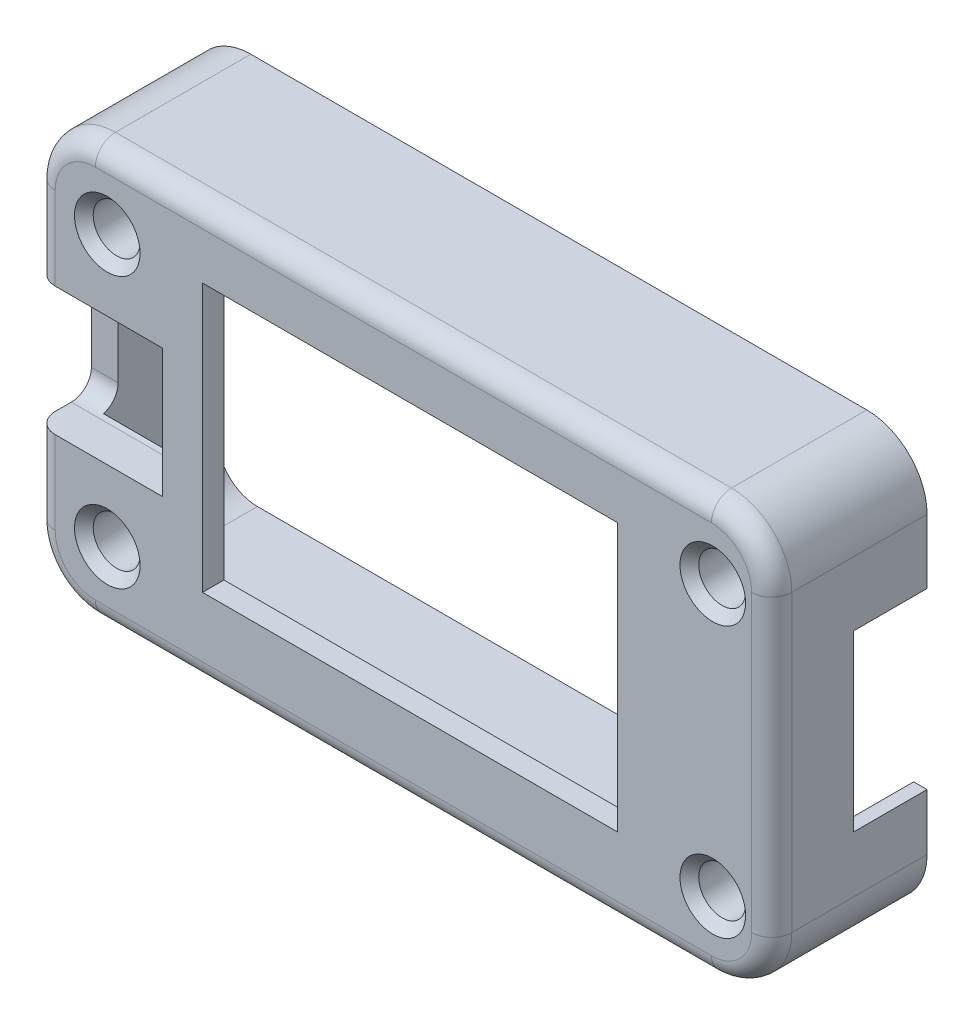
SolidWorks part; units mm, degrees
ref_plane "前视基准面" through (0, 0, 0) normal (0, 0, 1) x (1, 0, 0)
ref_plane "上视基准面" through (0, 0, 0) normal (0, 1, 0) x (1, 0, 0)
ref_plane "右视基准面" through (0, 0, 0) normal (1, 0, 0) x (0, 0, -1)
sketch "草图1" plane through (0, 0, 0) normal (0, 0, 1) x (1, 0, 0)
  line L0 (0, 0) -> (55, 0)
  line L1 (55, 0) -> (55, -31)
  line L2 (55, -31) -> (0, -31)
  line L3 (0, -31) -> (0, 0)
  line L4 (2, -2) -> (54, -2)
  line L5 (54, -2) -> (54, -29)
  line L6 (54, -29) -> (2, -29)
  line L7 (2, -29) -> (2, -2)
  dimension "D1" = 52
  dimension "D2" = 27
  dimension "D3" = 1
  dimension "D4" = 2
  dimension "D5" = 2
  dimension "D6" = 2
extrude "凸台-拉伸1" add sketch "草图1" along normal blind 10
sketch "草图2" plane through (0, 0, 10) normal (0, 0, 1) x (1, 0, 0)
  line L0 (55, -31) -> (55, 0) construction
  line L1 (0, -31) -> (55, -31) construction
  line L2 (0, 0) -> (0, -31) construction
  line L3 (55, 0) -> (0, 0) construction
  line L4 (55, -31) -> (55, 0)
  line L5 (0, -31) -> (55, -31)
  line L6 (0, 0) -> (0, -31)
  line L7 (55, 0) -> (0, 0)
extrude "凸台-拉伸2" add sketch "草图2" along normal blind 1.6
sketch "草图3" plane through (0, 0, 11.6) normal (0, 0, 1) x (1, 0, 0)
  line L0 (12.5, -5) -> (43.5, -5)
  line L1 (43.5, -5) -> (43.5, -25)
  line L2 (43.5, -25) -> (12.5, -25)
  line L3 (12.5, -25) -> (12.5, -5)
  line L4 (0, 0) -> (0, -31) construction
  line L8 (0, -31) -> (55, -31) construction
  dimension "D1" = 31
  dimension "D2" = 20
  dimension "D3" = 12.5
  dimension "D4" = 6
extrude "切除-拉伸1" cut sketch "草图3" against normal up to next
sketch "草图4" plane through (0, 0, 10) normal (0, 0, -1) x (-1, 0, 0)
  line L0 (-45.5, -3) -> (-10.5, -3)
  line L1 (-10.5, -3) -> (-10.5, -27)
  line L2 (-10.5, -27) -> (-45.5, -27)
  line L3 (-45.5, -27) -> (-45.5, -3)
  line L4 (-2, -29) -> (-54, -29) construction
  line L5 (-54, -29) -> (-54, -2) construction
  line L6 (-54, -2) -> (-2, -2) construction
  line L7 (-2, -2) -> (-2, -29) construction
  line L8 (-2, -29) -> (-54, -29)
  line L9 (-54, -29) -> (-54, -2)
  line L10 (-54, -2) -> (-2, -2)
  line L11 (-2, -2) -> (-2, -29)
  line L13 (-12.5, -25) -> (-12.5, -5) construction
  line L14 (-43.5, -5) -> (-43.5, -25) construction
  dimension "D1" = 1
  dimension "D2" = 2
  dimension "D3" = 2
  dimension "D4" = 2
extrude "凸台-拉伸3" add sketch "草图4" along normal blind 1.5
sketch "草图5" plane through (0, 0, 8.5) normal (0, 0, -1) x (-1, 0, 0)
  line L0 (-35.5, -27) -> (-20.5, -27)
  line L1 (-45.5, -27) -> (-10.5, -27) construction
  line L2 (-20.5, -27) -> (-20.5, -29)
  line L3 (-2, -29) -> (-54, -29) construction
  line L4 (-20.5, -29) -> (-35.5, -29)
  line L5 (-35.5, -29) -> (-35.5, -27)
  line L6 (-45.5, -3) -> (-45.5, -27) construction
  line L7 (-10.5, -27) -> (-10.5, -3) construction
  dimension "D1" = 10
  dimension "D2" = 10
extrude "切除-拉伸2" cut sketch "草图5" against normal blind 1.5
sketch "草图7" plane through (0, 0, 11.6) normal (0, 0, 1) x (1, 0, 0)
  line L0 (0, -10.7) -> (9.5, -10.7)
  line L1 (0, 0) -> (0, -31) construction
  line L2 (9.5, -10.7) -> (9.5, -20.3)
  line L3 (9.5, -20.3) -> (0, -20.3)
  line L4 (0, -20.3) -> (0, -10.7)
  line L5 (55, 0) -> (0, 0) construction
  dimension "D1" = 9.6
  dimension "D2" = 10.7
  dimension "D3" = 9.5
extrude "切除-拉伸4" cut sketch "草图7" against normal blind 4.2
sketch "草图8" plane through (0, 0, 8.5) normal (0, 0, -1) x (-1, 0, 0)
  line L0 (-9.5, -10.7) -> (-10.5, -10.7)
  line L1 (-10.5, -27) -> (-10.5, -3) construction
  line L2 (-10.5, -10.7) -> (-10.5, -20.3)
  line L3 (-10.5, -27) -> (-10.5, -3) construction
  line L4 (-10.5, -20.3) -> (-9.5, -20.3)
  line L5 (-9.5, -20.3) -> (-9.5, -10.7)
extrude "切除-拉伸5" cut sketch "草图8" against normal blind 1.5
sketch "草图9" plane through (0, 0, 0) normal (0, 0, -1) x (-1, 0, 0)
  line L0 (-55, -9.3) -> (-54, -9.3)
  line L1 (-55, -31) -> (-55, 0) construction
  line L2 (-54, -29) -> (-54, -2) construction
  line L3 (-54, -9.3) -> (-54, -22.3)
  line L4 (-54, -22.3) -> (-55, -22.3)
  line L5 (-55, -22.3) -> (-55, -9.3)
  line L6 (-54, -2) -> (-2, -2) construction
  dimension "D1" = 13
  dimension "D2" = 7.3
extrude "切除-拉伸6" cut sketch "草图9" against normal blind 5.5
sketch "草图10" plane through (0, 0, 8.5) normal (0, 0, -1) x (-1, 0, 0)
  line L0 (-54, -2) -> (-54, -29) construction
  line L2 (-54, -2) -> (-2, -2) construction
  circle A0 centre (-50.6, -5.4) radius 1.75
  circle A1 centre (-5.388, -5.4) radius 1.75
  circle A2 centre (-5.388, -25.6) radius 1.75
  circle A3 centre (-50.6, -25.6) radius 1.75
  dimension "D1" = 45.212
  dimension "D3" = 3.5
  dimension "D2" = 20.2
  dimension "D4" = 3.4
  dimension "D5" = 3.4
extrude "切除-拉伸7" cut sketch "草图10" against normal through all
fillet "圆角1" radius 3 4 edges at (2, -29, 4.25) (54, -29, 4.25) (54, -2, 4.25) (2, -2, 4.25)
fillet "圆角2" radius 4.5 4 edges at (0, 0, 5.8) (0, -31, 5.8) (55, -31, 5.8) (55, 0, 5.8)
fillet "圆角3" radius 1.5 2 edges at (1, -20.3, 7.4) (1, -10.7, 7.4)
fillet "圆角4" radius 1.5 9 edges at (0, -23.4, 11.6) (1.318, -29.682, 11.6) (0, -7.6, 11.6) (1.318, -1.318, 11.6) (27.5, 0, 11.6) (53.682, -1.318, 11.6) (55, -15.5, 11.6) (53.682, -29.682, 11.6) (27.5, -31, 11.6)
chamfer "倒角1" distance 0.7 angle 45 4 edges at (3.638, -5.4, 11.6) (3.638, -25.6, 11.6) (48.85, -5.4, 11.6) (48.85, -25.6, 11.6)
